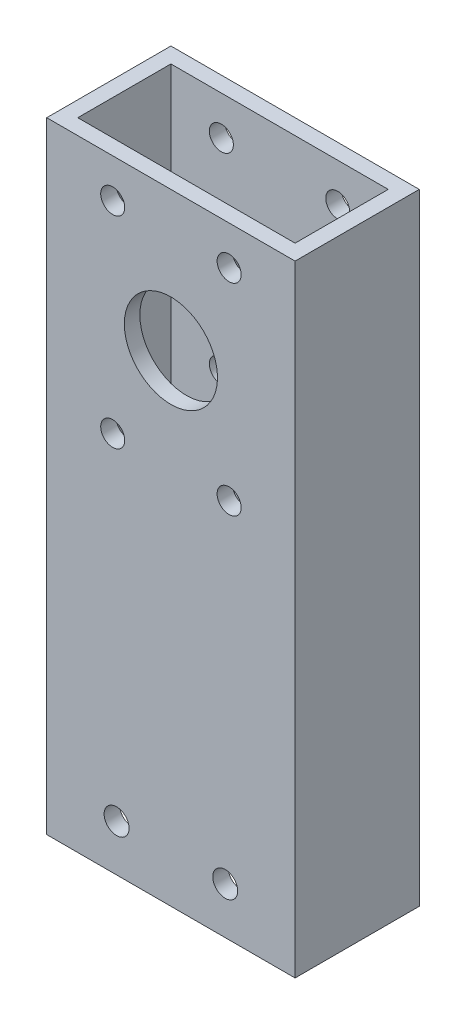
SolidWorks part; units mm, degrees
material "6061-T6 (SS)"
ref_plane "Front" through (0, 0, 0) normal (0, 0, 1) x (1, 0, 0)
ref_plane "Top" through (0, 0, 0) normal (0, 1, 0) x (1, 0, 0)
ref_plane "Right" through (0, 0, 0) normal (1, 0, 0) x (0, 0, -1)
sketch "Sketch1" plane through (0, 0, 0) normal (0, 1, 0) x (1, 0, 0)
  line L1 (-25.4, -12.7) -> (25.4, -12.7)
  line L2 (-25.4, -12.7) -> (-25.4, 12.7)
  line L3 (-25.4, 12.7) -> (25.4, 12.7)
  line L4 (25.4, -12.7) -> (25.4, 12.7)
  line L5 (-25.4, -12.7) -> (25.4, 12.7) construction
  line L6 (-25.4, 12.7) -> (25.4, -12.7) construction
  point P0 (0, 0)
  dimension "D1" = 25.4
  dimension "D2" = 50.8
extrude "Extrude-Thin1" add sketch "Sketch1" along normal blind 127 thin thin type one direction reverse wall 3.175
sketch "Sketch2" plane through (0, 0, -12.7) normal (0, 0, -1) x (-1, 0, 0)
  line L0 (0, 127) -> (0, 95.25)
  line L1 (-25.4, 127) -> (25.4, 127) construction
  line L3 (0, 85.725) -> (0, 104.775) construction
  circle A1 centre (0, 95.25) radius 23.8125
  circle A3 centre (0, 95.25) radius 9.525
  point P12 (0, 95.25)
  dimension "D1" = 19.05
  dimension "D3" = 47.625
  dimension "D2" = 31.75
hole_wizard "#10 (0.1935) Diameter Hole2" positions "Sketch5" profile "Sketch6" hole size "#10" standard "ANSI Inch" end condition through all
sketch "Sketch5" plane through (0, 0, -12.7) normal (0, 0, -1) x (-1, 0, 0)
  line L0 (0, 127) -> (0, 98.425)
  line L1 (-25.4, 127) -> (25.4, 127) construction
  line L3 (-11.9063, 119.0472) -> (11.9063, 119.0472)
  line L4 (-11.9063, 119.0472) -> (-11.9063, 77.8028)
  line L5 (-11.9063, 77.8028) -> (11.9063, 77.8028)
  line L6 (11.9063, 119.0472) -> (11.9063, 77.8028)
  circle A0 centre (0, 98.425) radius 23.8125
  point P21 (-11.9063, 119.0472)
  point P22 (11.9063, 119.0472)
  point P24 (11.9063, 77.8028)
  point P25 (-11.9062, 77.8028)
  dimension "D1" = 47.625
  dimension "D2" = 28.575
  dimension "D3" = 23.8125
sketch "Sketch6" plane through (11.9062, 77.8028, -12.7) normal (1, 0, 0) x (0, 1, 0)
  line L0 (0, 0) -> (0, 25.4)
  line L1 (0, 25.4) -> (2.4574, 25.4)
  line L2 (2.4574, 25.4) -> (2.4574, 0)
  line L5 (2.4574, 0) -> (0, 0)
  line L11 (0, -6.35) -> (0, 107.95) construction
  dimension "Thru Hole Dia." = 4.9149
  dimension "Thru Hole Depth" = 25.4
sketch "Sketch7" plane through (0, 0, -12.7) normal (0, 0, -1) x (-1, 0, 0)
  line L0 (-11.9063, 119.0472) -> (11.9063, 77.8028) construction
  circle A1 centre (0, 98.425) radius 9.525
  point P9 (0, 98.425)
  dimension "D1" = 19.05
extrude "Cut-Extrude2" cut sketch "Sketch7" against normal through all both
hole_wizard "1/4-20 Tapped Hole1" positions "Sketch8" profile "Sketch9" tap size "1/4-20" standard "ANSI Inch" end condition through all
sketch "Sketch8" plane through (0, 0, 12.7) normal (0, 0, 1) x (1, 0, 0)
  line L2 (-25.4, 127) -> (-25.4, 0) construction
  line L4 (-25.4, 0) -> (25.4, 0) construction
  point P0 (-11.1125, 9.525)
  point P2 (11.1125, 9.525)
  point P14 (-109.1715, 68.7854)
  dimension "D1" = 22.225
  dimension "D2" = 14.2875
  dimension "D3" = 9.525
sketch "Sketch9" plane through (-11.1125, 9.525, 12.7) normal (1, 0, 0) x (0, -1, 0)
  line L0 (0, 0) -> (0, 25.4)
  line L1 (0, 25.4) -> (2.5527, 25.4)
  line L2 (2.5527, 25.4) -> (2.5527, 0)
  line L5 (2.5527, 0) -> (0, 0)
  line L11 (0, -6.35) -> (0, 107.95) construction
  dimension "Thru Tap Drill Dia." = 5.1054
  dimension "Thru Tap Drill Depth" = 25.4
cosmetic thread "Hole Thread1" parameters "D2"=6.35
cosmetic thread "Hole Thread2" parameters "D2"=6.35
